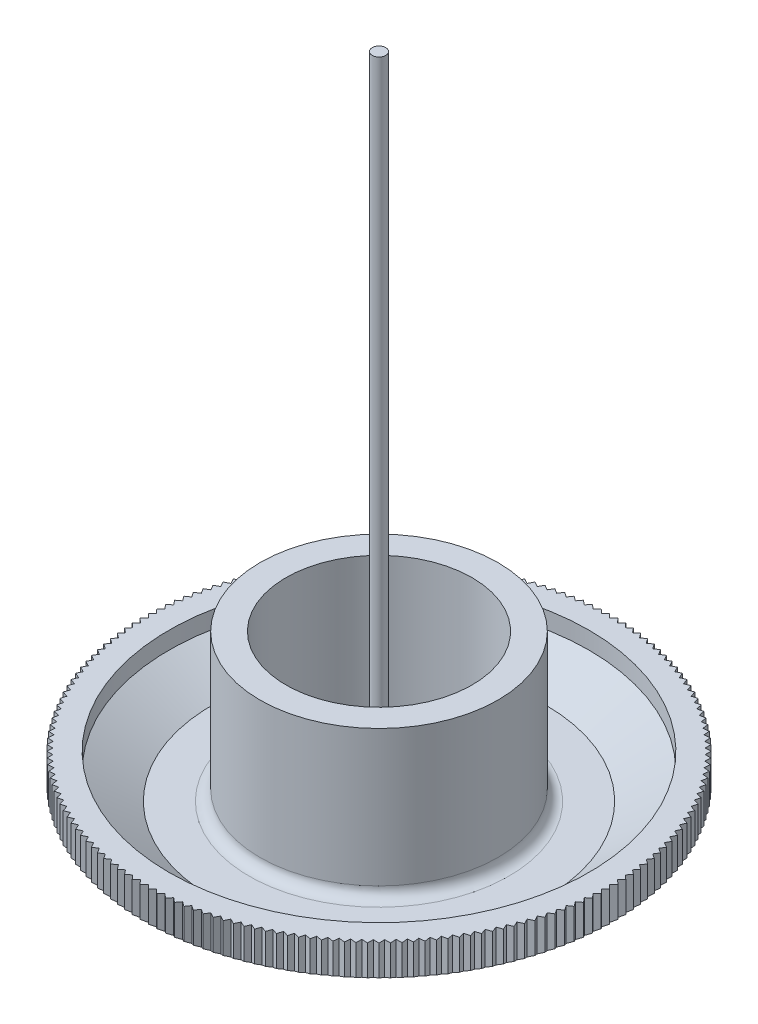
SolidWorks part; units mm, degrees
note: '?' marks a value the reader was unsure of.
ref_plane "YZ" through (0, 0, 0) normal (0, 0, 1) x (1, 0, 0)
ref_plane "XY" through (0, 0, 0) normal (0, 1, 0) x (1, 0, 0)
ref_plane "XZ" through (0, 0, 0) normal (1, 0, 0) x (0, 0, -1)
sketch "Sketch1" plane through (0, 0, 0) normal (0, 0, 1) x (1, 0, 0)
  line L0 (0, 0) -> (19.939, 0)
  line L1 (19.939, 0) -> (27.559, 4.572)
  line L2 (0, 0) -> (0, 3.048)
  line L3 (0, 3.048) -> (10.922, 3.048)
  line L4 (10.922, 3.048) -> (10.922, 20.32)
  line L5 (10.922, 20.32) -> (13.97, 20.32)
  line L6 (13.97, 20.32) -> (13.97, 4.318)
  line L7 (15.24, 3.048) -> (19.558, 3.048)
  line L8 (19.558, 3.048) -> (24.638, 6.096)
  line L9 (24.638, 6.096) -> (24.638, 8.128)
  line L10 (24.638, 8.128) -> (27.559, 8.128)
  line L11 (27.559, 8.128) -> (27.559, 4.572)
  line L12 (0, 0) -> (0, 23.1014) construction
  arc A0 (13.97, 4.318) -> (15.24, 3.048) centre (15.24, 4.318) ccw
  dimension "D11" = 1.27
  dimension "D1" = 13.97
  dimension "D2" = 20.32
  dimension "D3" = 17.272
  dimension "D4" = 3.048
  dimension "D5" = 2.921
  dimension "D6" = 2.032
  dimension "D7" = 19.939
  dimension "D8" = 8.128
  dimension "D9" = 5.588
  dimension "D10" = 27.559
revolve "Base-Revolve" add sketch "Sketch1" angle 360 about L12
sketch "Sketch2" plane through (0, 8.128, 0) normal (0, 1, 0) x (-1, 0, 0)
  line L0 (0, 0) -> (0, -27.559) construction
  line L1 (0, 0) -> (-0.481, -27.5548) construction
  line L2 (0, 0) -> (0.481, -27.5548) construction
  line L3 (0.481, -27.5548) -> (0, -27.0738)
  line L4 (0, -27.0738) -> (-0.481, -27.5548)
  circle A0 centre (0, 0) radius 27.559 construction
  dimension "D1" = 1
  dimension "D2" = 1
extrude "Cut-Extrude1" cut sketch "Sketch2" against normal through all
ref_axis "Axis1" through (0, 53.048, 0) along (0, -1, 0)?
pattern_circular "CirPattern1" count 180 every 2 about axis through (0, 53.048, 0) along (0, -1, 0)
sketch "Sketch3" plane through (0, 0, 0) normal (0, -1, 0) x (1, 0, 0)
  line L0 (0, 0) -> (16.383, 0) construction
  line L1 (0, 0) -> (-8.1915, 14.1881) construction
  line L2 (0, 0) -> (-8.1915, -14.1881) construction
  line L3 (15.5571, -5.334) -> (17.4621, 0)
  line L4 (15.5571, -5.334) -> (13.6521, 0)
  line L5 (17.4621, 0) -> (13.6521, 0) construction
  line L6 (15.5571, -5.334) -> (15.5571, 0) construction
  line L7 (0, 0) -> (13.6521, 0) construction
  line L8 (0, 0) -> (9.7836, 16.9457) construction
  line L9 (8.1915, 14.1881) -> (7.366, 12.7583)
  line L10 (17.4621, 0) -> (16.383, 0)
  line L12 (14.732, 0) -> (13.6521, 0)
  arc A1 (14.732, 0) -> (7.366, 12.7583) centre (0, 0) ccw
  circle A2 centre (0, 0) radius 15.5575 construction
  arc A3 (16.383, 0) -> (8.1915, 14.1881) centre (0, 0) ccw
  dimension "D2" = 29.464
  dimension "D5" = 31.115
  dimension "D3" = 120
  dimension "D4" = 120
  dimension "D6" = 5.334
  dimension "D7" = 3.81
  dimension "D8" = 60
extrude "Boss-Extrude1" add sketch "Sketch3" along normal blind 0.254
pattern_circular "CirPattern2" count 3 every 120 about axis through (0, 53.048, 0) along (0, -1, 0)
sketch "Sketch4" plane through (0, 3.048, 0) normal (0, 1, 0) x (-1, 0, 0)
  circle A0 centre (0, 0) radius 0.7937
  dimension "D1" = 1.5875
extrude "Boss-Extrude2" add sketch "Sketch4" along normal blind 76.2
